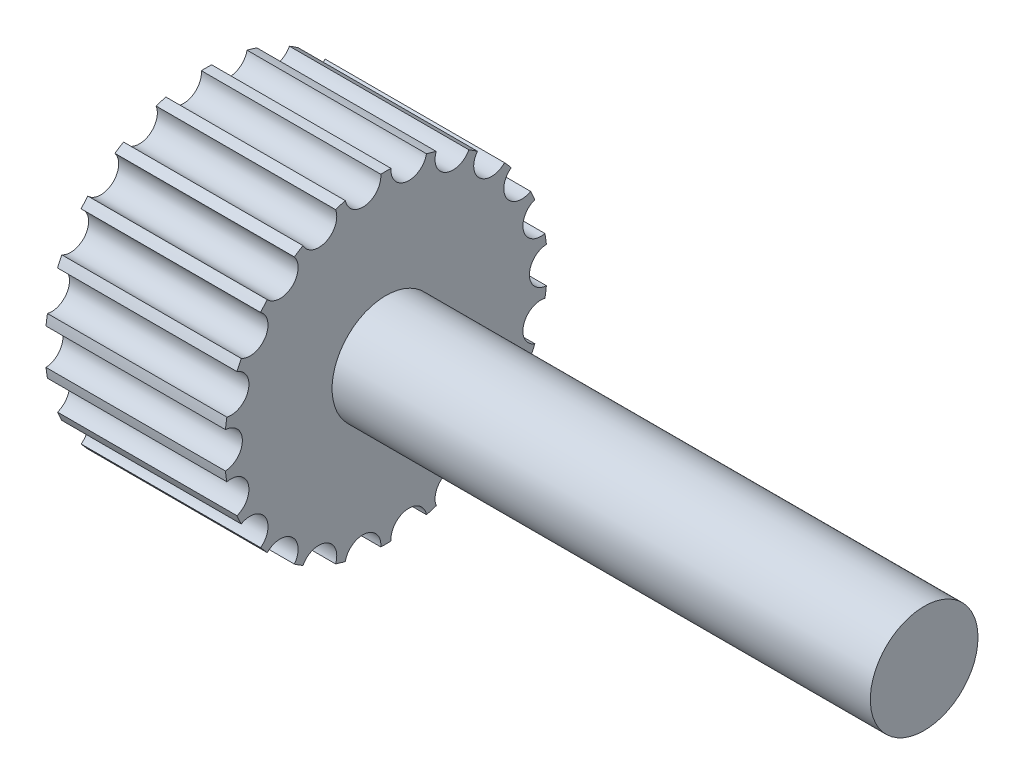
SolidWorks part; units mm, degrees
material "Brass"
ref_plane "Front Plane" through (0, 0, 0) normal (0, 0, 1) x (1, 0, 0)
ref_plane "Top Plane" through (0, 0, 0) normal (0, 1, 0) x (1, 0, 0)
ref_plane "Right Plane" through (0, 0, 0) normal (1, 0, 0) x (0, 0, -1)
sketch "Sketch1" plane through (0, 0, 0) normal (1, 0, 0) x (0, 0, -1)
  circle A0 centre (0, 0) radius 4.5
  dimension "D1" = 9
extrude "Boss-Extrude1" add sketch "Sketch1" along normal blind 5
sketch "Sketch2" plane through (0, 0, 0) normal (1, 0, 0) x (0, 0, -1)
  circle A0 centre (0, 0) radius 1.5
  dimension "D1" = 3
extrude "Boss-Extrude2" add sketch "Sketch2" along normal blind 20
cosmetic thread "Cosmetic Thread1" parameters "D1"=15, "D2"=0
sketch "Sketch3" plane through (0, 0, 0) normal (1, 0, 0) x (0, 0, -1)
  circle A0 centre (4.5, 0) radius 0.5
  dimension "D2" = 1
  dimension "D1" = 4.5
extrude "Cut-Extrude2" cut sketch "Sketch3" against normal blind 5 and the other way blind 5
ref_axis "Axis1" through (-1, 0, 0) along (1, 0, 0)
pattern_circular "CirPattern1" count 22 over 360 about axis through (-1, 0, 0) along (1, 0, 0) of "Cut-Extrude2"
